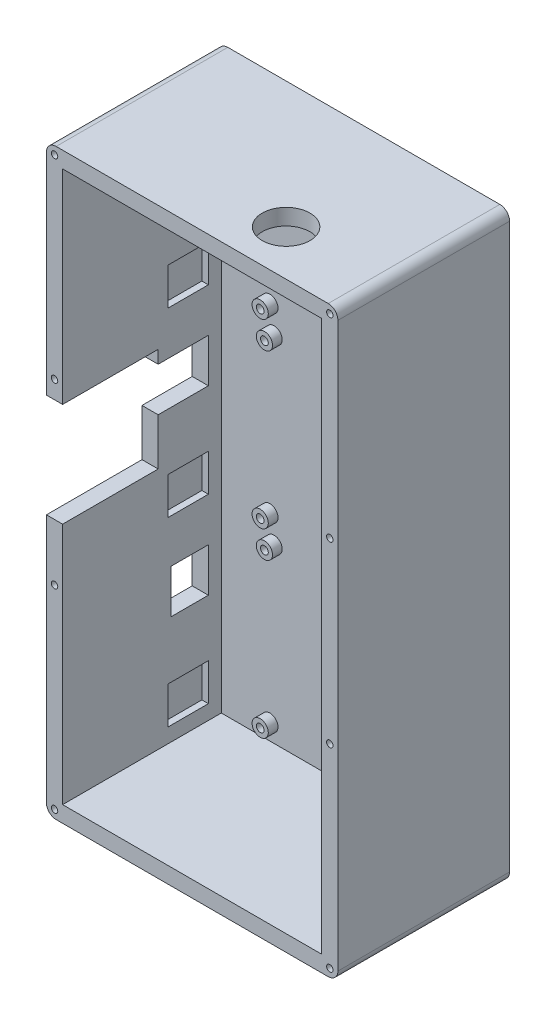
SolidWorks part; units mm, degrees
ref_plane "Front Plane" through (0, 0, 0) normal (0, 0, 1) x (1, 0, 0)
ref_plane "Top Plane" through (0, 0, 0) normal (0, 1, 0) x (1, 0, 0)
ref_plane "Right Plane" through (0, 0, 0) normal (1, 0, 0) x (0, 0, -1)
sketch "Sketch2" plane through (0, 0, 0) normal (0, 0, 1) x (1, 0, 0)
  line L1 (-45, 90) -> (45, 90)
  line L2 (-45, 90) -> (-45, -90)
  line L3 (-45, -90) -> (45, -90)
  line L4 (45, 90) -> (45, -90)
  point P4 (0, 90)
  point P6 (-45, 0)
  dimension "D1" = 180
  dimension "D2" = 90
extrude "Boss-Extrude1" add sketch "Sketch2" along normal blind 53
sketch "Sketch3" plane through (0, 0, 53) normal (0, 0, 1) x (1, 0, 0)
  line L0 (45, -90) -> (45, 90) construction
  line L1 (-40, 85) -> (40, 85)
  line L2 (-40, 85) -> (-40, -85)
  line L3 (-40, -85) -> (40, -85)
  line L4 (40, 85) -> (40, -85)
  line L5 (45, 90) -> (-45, 90) construction
  point P4 (0, 85)
  point P6 (-40, 0)
  dimension "D1" = 5
  dimension "D2" = 5
extrude "Cut-Extrude1" cut sketch "Sketch3" against normal blind 49
sketch "Sketch6" plane through (0, 0, 4) normal (0, 0, 1) x (1, 0, 0)
  circle A0 centre (-23.7, 24.2) radius 2.5
  circle A1 centre (-25, -24) radius 2.5
  circle A2 centre (27.1, 9) radius 2.5
  circle A3 centre (27.1, -18.9) radius 2.5
  dimension "D5" = 5
  dimension "D1" = 50.8
  dimension "D2" = 27.9
  dimension "D3" = 15.2
  dimension "D4" = 48.2
  dimension "D6" = 23.7
  dimension "D7" = 24
  dimension "D8" = 1.3
extrude "Boss-Extrude2" add sketch "Sketch6" along normal blind 3
hole_wizard "M2 Clearance Hole1" positions "Sketch9" profile "Sketch8" hole size "M2" standard "ANSI Metric" end condition through all
sketch "Sketch9" plane through (0, 0, 7) normal (0, 0, 1) x (1, 0, 0)
  point P0 (-23.7, 24.2)
  point P3 (27.1, 9)
  point P6 (27.1, -18.9)
  point P9 (-25, -24)
sketch "Sketch8" plane through (-23.7, 24.2, 7) normal (1, 0, 0) x (0, -1, 0)
  line L0 (0, 0) -> (0, 7)
  line L1 (0, 7) -> (1.2, 7)
  line L2 (1.2, 7) -> (1.2, 0)
  line L5 (1.2, 0) -> (0, 0)
  line L11 (0, -6.35) -> (0, 107.95) construction
  dimension "Thru Hole Dia." = 2.4
  dimension "Thru Hole Depth" = 7
sketch "Sketch17" plane through (0, 0, 53) normal (0, 0, 1) x (1, 0, 0)
  line L0 (-45, 90) -> (-45, -90) construction
  line L1 (-45, 22) -> (-40, 22)
  line L2 (-45, 22) -> (-45, -10)
  line L3 (-45, -10) -> (-40, -10)
  line L4 (-40, 22) -> (-40, -10)
  line L5 (-40, 85) -> (-40, -85) construction
  dimension "D1" = 32
  dimension "D2" = 22
extrude "Cut-Extrude8" cut sketch "Sketch17" against normal blind 29.5
sketch "Sketch19" plane through (0, 0, 53) normal (0, 0, 1) x (1, 0, 0)
  line L0 (-45, 22) -> (-45, -10) construction
  line L1 (-45, 18) -> (-40, 18)
  line L2 (-45, 18) -> (-45, 4.5)
  line L3 (-45, 4.5) -> (-40, 4.5)
  line L4 (-40, 18) -> (-40, 4.5)
  line L5 (-40, -10) -> (-40, 22) construction
  dimension "D1" = 13.5
  dimension "D2" = 18
extrude "Cut-Extrude9" cut sketch "Sketch19" against normal blind 45
sketch "Sketch24" plane through (0, 0, 53) normal (0, 0, 1) x (1, 0, 0)
  line L0 (45, 90) -> (-45, 90) construction
  line L1 (-42.5, 87.5) -> (42.5, 87.5) construction
  line L2 (-42.5, 87.5) -> (-42.5, -87.5) construction
  line L3 (-42.5, -87.5) -> (42.5, -87.5) construction
  line L4 (42.5, 87.5) -> (42.5, -87.5) construction
  line L5 (45, -90) -> (45, 90) construction
  circle A0 centre (-42.5, 87.5) radius 1
  circle A1 centre (42.5, 87.5) radius 1
  circle A2 centre (42.5, -87.5) radius 1
  circle A3 centre (-42.5, -87.5) radius 1
  circle A4 centre (-42.5, 27.5) radius 1
  circle A5 centre (42.5, 27.5) radius 1
  circle A6 centre (-42.5, -27.5) radius 1
  circle A7 centre (42.5, -27.5) radius 1
  point P4 (0, 87.5)
  point P6 (-42.5, 0)
  dimension "D1" = 2
  dimension "D4" = 2
  dimension "D5" = 2
  dimension "D8" = 2
  dimension "D9" = 2
  dimension "D2" = 2.5
  dimension "D3" = 2.5
  dimension "D6" = 60
  dimension "D7" = 60
  dimension "D10" = 60
  dimension "D11" = 60
fillet "Fillet2" radius 3 4 edges at (-45, 90, 26.5) (45, 90, 26.5) (45, -90, 26.5) (-45, -90, 26.5)
pattern_linear "LPattern1" count 2 spacing 56 along (0, 1, 0) of "Boss-Extrude2", "M2 Clearance Hole1"
pattern_linear "LPattern2" count 2 spacing 56 along (0, -1, 0) of "Boss-Extrude2", "M2 Clearance Hole1"
ref_axis "Axis1" through (-23.7, 80.2, 0) along (0, 0, 1)
sketch "Sketch30" plane through (-45, 0, 0) normal (-1, 0, 0) x (0, 0, 1)
  line L0 (8, -38.4995) -> (8, 92.514) construction
  line L1 (8, 18) -> (8, 4.5) construction
sketch "Sketch29" plane through (-45, 0, 0) normal (-1, 0, 0) x (0, 0, 1)
  line L0 (0, 80.2) -> (7, 80.2) construction
  line L1 (8, 60.5) -> (19.5, 60.5)
  line L2 (8, 60.5) -> (8, 74)
  line L3 (8, 74) -> (19.5, 74)
  line L4 (19.5, 60.5) -> (19.5, 74)
  line L5 (8, -200038.4995) -> (8, 200092.514) construction
  dimension "D1" = 11.5
  dimension "D2" = 13.5
  dimension "D3" = 6.2
ref_axis "Axis2" through (-23.7, 24.2, 0) along (0, 0, 1)
ref_axis "Axis3" through (-23.7, -31.8, 0) along (0, 0, 1)
extrude "Cut-Extrude12" cut sketch "Sketch29" against normal blind 10
pattern_linear "LPattern4" count 2 spacing 112 along (0, -1, 0) of "Cut-Extrude12"
ref_axis "Axis4" through (-25, 32, 0) along (0, 0, 1)
ref_axis "Axis5" through (-25, -24, 0) along (0, 0, 1)
ref_axis "Axis6" through (-25, -80, 0) along (0, 0, 1)
sketch "Sketch32" plane through (-40, 0, 0) normal (1, 0, 0) x (0, 0, -1)
  line L0 (-8, -200038.4995) -> (-8, 200092.514) construction
  line L1 (-20.5, 31.5) -> (-8, 31.5)
  line L2 (-20.5, 31.5) -> (-20.5, 43)
  line L3 (-20.5, 43) -> (-8, 43)
  line L4 (-8, 31.5) -> (-8, 43)
  line L6 (0, 32) -> (-7, 32) construction
  point P8 (-8, 37.25)
  dimension "D1" = 12.5
  dimension "D2" = 11.5
  dimension "D3" = 5.25
extrude "Cut-Extrude13" cut sketch "Sketch32" against normal blind 2
pattern_linear "LPattern5" count 3 spacing 56 along (0, -1, 0) of "Cut-Extrude13"
sketch "Sketch33" plane through (40, 0, 0) normal (-1, 0, 0) x (0, 0, 1)
  line L0 (4, -85) -> (4, 85) construction
  line L1 (42, -30) -> (34, -30)
  line L2 (42, -30) -> (42, -40)
  line L3 (42, -40) -> (34, -40)
  line L4 (34, -30) -> (34, -40)
  line L5 (4, -85) -> (53, -85) construction
  dimension "D1" = 10
  dimension "D2" = 8
  dimension "D3" = 30
  dimension "D4" = 45
extrude "Boss-Extrude3" add sketch "Sketch33" along normal blind 5.5
sketch "Sketch34" plane through (0, 0, 42) normal (0, 0, 1) x (1, 0, 0)
  line L0 (34.5, -30) -> (40, -30) construction
  line L1 (36.5, -37.5) -> (40, -37.5)
  line L2 (36.5, -37.5) -> (36.5, -32.5)
  line L3 (36.5, -32.5) -> (40, -32.5)
  line L4 (40, -37.5) -> (40, -32.5)
  line L5 (34.5, -40) -> (40, -40) construction
  line L6 (34.5, -40) -> (34.5, -30) construction
  line L7 (40, -40) -> (40, -30) construction
  point P4 (38.25, -32.5)
  point P9 (37.25, -40)
  dimension "D1" = 2.5
  dimension "D2" = 2.5
  dimension "D3" = 2
extrude "Cut-Extrude14" cut sketch "Sketch34" against normal up to next
sketch "Sketch35" plane through (34.5, 0, 0) normal (-1, 0, 0) x (0, 0, 1)
  line L0 (42, -40) -> (42, -30) construction
  line L1 (40, -30) -> (36, -30)
  line L2 (40, -30) -> (40, -40)
  line L3 (40, -40) -> (36, -40)
  line L4 (36, -30) -> (36, -40)
  line L5 (34, -30) -> (34, -40) construction
  line L6 (34, -40) -> (42, -40) construction
  line L7 (42, -30) -> (34, -30) construction
  dimension "D1" = 2
  dimension "D2" = 2
extrude "Cut-Extrude15" cut sketch "Sketch35" against normal blind 5.5
pattern_linear "LPattern6" count 3 spacing 56 along (0, 1, 0) of "Boss-Extrude3", "Cut-Extrude14", "Cut-Extrude15"
sketch "Sketch36" plane through (0, 90, 0) normal (0, 1, 0) x (1, 0, 0)
  line L0 (-42.5, -53) -> (42.5, -53) construction
  line L1 (45, 0) -> (45, -53) construction
  circle A0 centre (15, -39) radius 7.375
  dimension "D1" = 14.75
  dimension "D2" = 14
  dimension "D3" = 30
extrude "Cut-Extrude16" cut sketch "Sketch36" against normal blind 10
extrude "Cut-Extrude17" cut sketch "Sketch24" against normal through all
